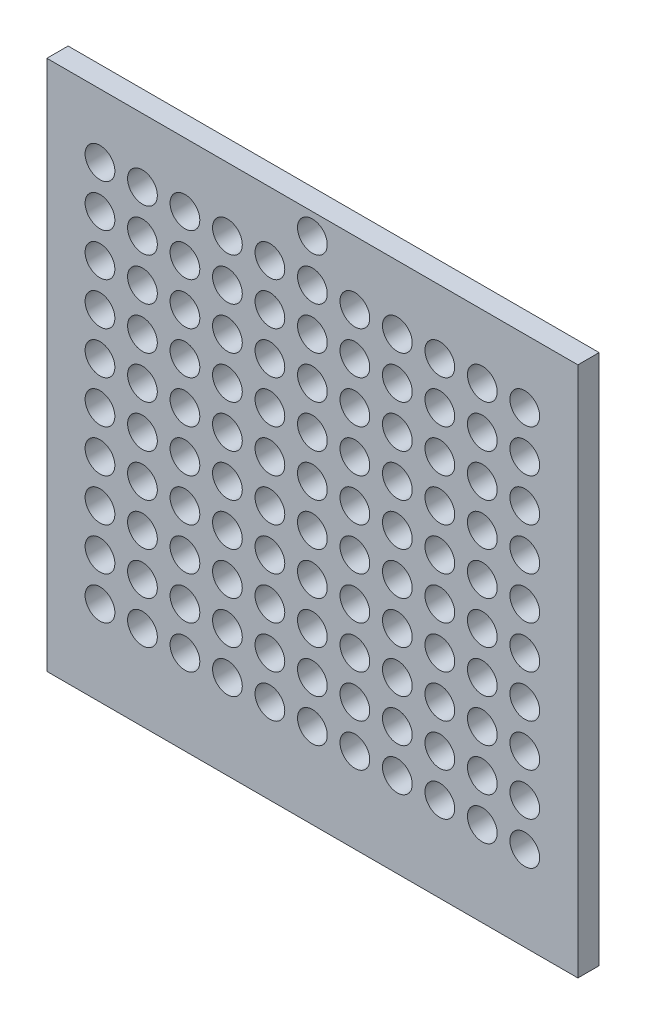
SolidWorks part; units mm, degrees
ref_plane "Ebene vorne" through (0, 0, 0) normal (0, 0, 1) x (1, 0, 0)
ref_plane "Ebene oben" through (0, 0, 0) normal (0, 1, 0) x (1, 0, 0)
ref_plane "Ebene rechts" through (0, 0, 0) normal (1, 0, 0) x (0, 0, -1)
sketch "Skizze2" plane through (0, 0, 0) normal (0, 0, 1) x (1, 0, 0)
  line L0 (-62.5, 62.5) -> (-62.5, -62.5) construction
  line L1 (-62.5, -62.5) -> (62.5, -62.5) construction
  line L2 (62.5, 62.5) -> (-62.5, 62.5) construction
  line L3 (62.5, -62.5) -> (62.5, 62.5) construction
  line L4 (-62.5, 62.5) -> (-62.5, -62.5)
  line L5 (-62.5, -62.5) -> (62.5, -62.5)
  line L6 (62.5, 62.5) -> (-62.5, 62.5)
  line L7 (62.5, -62.5) -> (62.5, 62.5)
extrude "Aufsatz-Linear austragen1" add sketch "Skizze2" along normal blind 5
sketch "Skizze3" plane through (0, 0, 0) normal (0, 0, -1) x (-1, 0, 0)
  line L0 (0, 62.5) -> (0, 0) construction
  line L1 (-62.5, 62.5) -> (62.5, 62.5) construction
  line L2 (-67.5, 67.5) -> (67.5, 67.5) construction
  circle A0 centre (0, 57.5) radius 3.5
  dimension "D1" = 7
  dimension "D2" = 10
extrude "Schnitt-Linear austragen1" cut sketch "Skizze3" against normal up to surface (5 mm away) up to face at (0, 0, 5)
sketch "Skizze4" plane through (0, 0, 0) normal (0, 0, -1) x (-1, 0, 0)
  line L0 (0, 0) -> (0, 62.5) construction
  line L1 (-62.5, 62.5) -> (62.5, 62.5) construction
  line L2 (-67.5, 67.5) -> (67.5, 67.5) construction
  circle A0 centre (0, 47.5) radius 3.5
  dimension "D1" = 7
  dimension "D2" = 20
extrude "Schnitt-Linear austragen2" cut sketch "Skizze4" against normal up to surface (5 mm away) up to face at (3.5, 57.5, 5)
pattern_linear "Lineares Muster1" count 6 spacing 10 along (1, 0, 0) count 10 spacing 10 along (0, -1, 0) of "Schnitt-Linear austragen2"
pattern_linear "Lineares Muster2" count 6 spacing 10 along (-1, 0, 0) count 10 spacing 10 along (0, -1, 0) skipping (0, 1), (0, 2), (0, 3), (0, 4), (0, 5), (0, 6), (0, 7), (0, 8), (0, 9) of "Schnitt-Linear austragen2"
